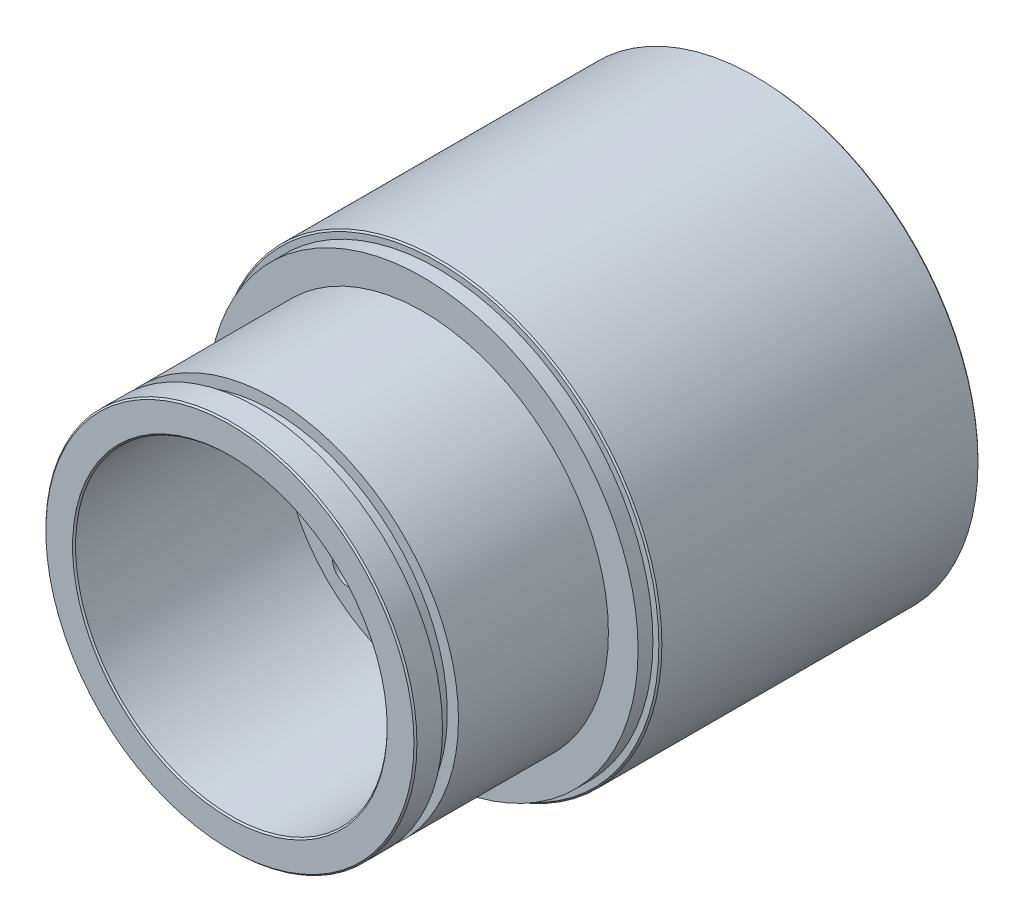
SolidWorks part; units mm, degrees
material "1060 Alloy"
ref_plane "Front Plane" through (0, 0, 0) normal (0, 0, 1) x (1, 0, 0)
ref_plane "Top Plane" through (0, 0, 0) normal (0, 1, 0) x (1, 0, 0)
ref_plane "Right Plane" through (0, 0, 0) normal (1, 0, 0) x (0, 0, -1)
sketch "Sketch1" plane through (0, 0, 0) normal (0, 1, 0) x (1, 0, 0)
  line L0 (0, 0) -> (0, 43) construction
  line L1 (13, 0) -> (21, 0)
  line L2 (21, 0) -> (21, -28)
  line L3 (21, -28) -> (25, -28)
  line L4 (25, -28) -> (25, -2)
  line L5 (29, 0) -> (30, 0)
  line L6 (30, 0) -> (30, 43)
  line L9 (30, 43) -> (20.5, 43)
  line L10 (20.5, 43) -> (20.5, 4)
  line L11 (20.5, 4) -> (13, 4)
  line L12 (13, 4) -> (13, 0)
  line L13 (25, -2) -> (29, -2)
  line L14 (29, -2) -> (29, 0)
  dimension "D1" = 26
  dimension "D2" = 50
  dimension "D3" = 4
  dimension "D4" = 4
  dimension "D5" = 41
  dimension "D6" = 39
  dimension "D7" = 58
  dimension "D10" = 2
  dimension "D11" = 60
  dimension "D12" = 26
revolve "Revolve1" add sketch "Sketch1" angle 360 about L0
sketch "Sketch2" plane through (0, 0, 0) normal (0, 1, 0) x (1, 0, 0)
  line L0 (25, -28) -> (25, -2) construction
  line L1 (25, -22.2) -> (23.5, -22.2)
  line L2 (25, -22.2) -> (25, -24.35)
  line L3 (25, -24.35) -> (23.5, -24.35)
  line L4 (23.5, -22.2) -> (23.5, -24.35)
  line L5 (0, 0) -> (0, -28) construction
  line L6 (-25, 0) -> (25, 0) construction
  line L7 (-25, -28) -> (25, -28) construction
  line L9 (-29, -2) -> (29, -2) construction
  dimension "D1" = 2.15
  dimension "D2" = 47
  dimension "D3" = 20.2
revolve "Cut-Revolve1" cut sketch "Sketch2" angle 360 about L5
chamfer "Chamfer1" distance 0.2 angle 45 5 edges at (30, 0, 0) (20.5, 0, -43) (25, 0, 28) (21, 0, 28) (30, 0, -43)
hole_wizard "M4 Clearance Hole1" positions "Sketch3" profile "Sketch4" hole size "M4" standard "ISO" end condition through all
sketch "Sketch3" plane through (0, 0, 0) normal (0, 0, 1) x (1, 0, 0)
  line L0 (-12.0208, 12.0208) -> (0, 0) construction
  line L2 (0, 0) -> (0, 8.8626) construction
  point P0 (-12.0208, 12.0208)
  dimension "D1" = 17
  dimension "D2" = 45
sketch "Sketch4" plane through (-12.0208, 12.0208, 0) normal (1, 0, 0) x (0, -1, 0)
  line L0 (0, 0) -> (0, 43)
  line L1 (0, 43) -> (2.15, 43)
  line L2 (2.15, 43) -> (2.15, 0)
  line L5 (2.15, 0) -> (0, 0)
  line L11 (0, -6.35) -> (0, 107.95) construction
  dimension "Thru Hole Dia." = 4.3
  dimension "Thru Hole Depth" = 43
pattern_circular "CirPattern1" count 4 over 360 about axis through (0, 0, 0) along (0, 0, 1) of "M4 Clearance Hole1"
hole_wizard "M4 Tapped Hole1" positions "Sketch8" profile "Sketch9" tap size "M4" standard "ISO"
sketch "Sketch8" plane through (0, 0, -43) normal (0, 0, -1) x (-1, 0, 0)
  point P0 (0, 25)
  dimension "D1" = 25
cosmetic thread "Hole Thread3" parameters "D1"=8, "D2"=4
sketch "Sketch9" plane through (0, 25, -43) normal (1, 0, 0) x (0, 1, 0)
  line L0 (0, 0) -> (0, 11.0914)
  line L1 (0, 11.0914) -> (1.65, 10.1)
  line L2 (1.65, 10.1) -> (1.65, 0)
  line L5 (1.65, 0) -> (0, 0)
  line L10 (0, 11.0914) -> (-1.65, 10.1) construction
  line L11 (0, -6.35) -> (0, 107.95) construction
  dimension "Tap Drill Dia." = 3.3
  dimension "Tap Drill Depth" = 10.1
  dimension "Drill Angle" = 118
pattern_circular "CirPattern3" count 6 over 360 about axis through (0, 0, 0) along (0, 0, 1) of "M4 Tapped Hole1" reverse direction yes
move or copy body "Body-Move/Copy1" [suppressed] bodies to move or copy 109
